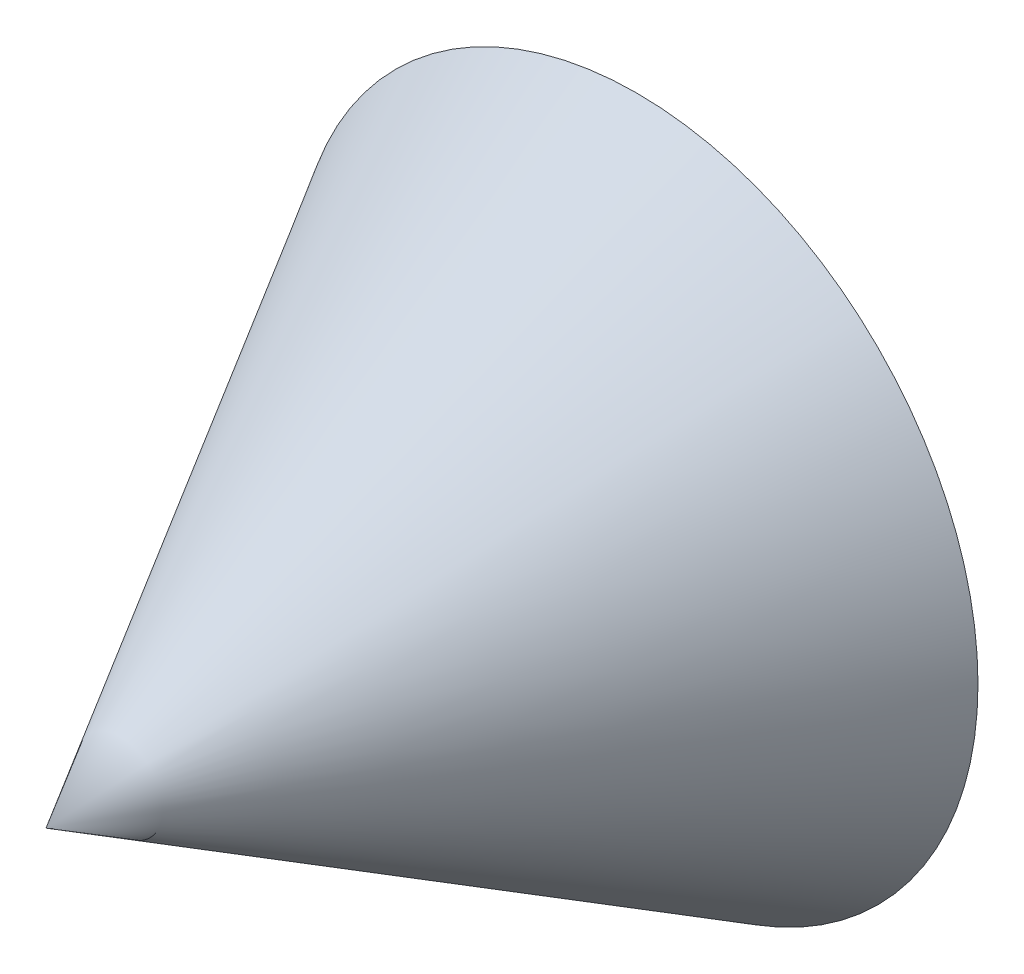
SolidWorks part; units mm, degrees
ref_plane "前基準面" through (0, 0, 0) normal (0, 0, 1) x (1, 0, 0)
ref_plane "上基準面" through (0, 0, 0) normal (0, 1, 0) x (1, 0, 0)
ref_plane "右基準面" through (0, 0, 0) normal (1, 0, 0) x (0, 0, -1)
sketch "草圖1" plane through (0, 0, 0) normal (1, 0, 0) x (0, 0, -1)
  line L0 (0, 0) -> (12.9904, 7.5)
  line L1 (0, 0) -> (2, 0)
  line L2 (0, 0) -> (75.9875, 0) construction
  line L3 (2, 0) -> (12.9904, 6.3453)
  line L4 (12.9904, 7.5) -> (12.9904, 6.3453)
  dimension "D1" = 30
  dimension "D3" = 7.5
  dimension "D5" = 1
revolve "旋轉1" add sketch "草圖1" angle 360 about L2
sketch "草圖4" plane through (0, 0, -12.9904) normal (0, 0, -1) x (-1, 0, 0)
  line L0 (0, 7.5) -> (0, -7.5) construction
  line L1 (-7.5, 0) -> (7.5, 0) construction
  circle A0 centre (0, 0) radius 7.5 construction
ref_plane "平面2" through (0, 0, 0) normal (0, 1, 0) x (1, 0, 0)
